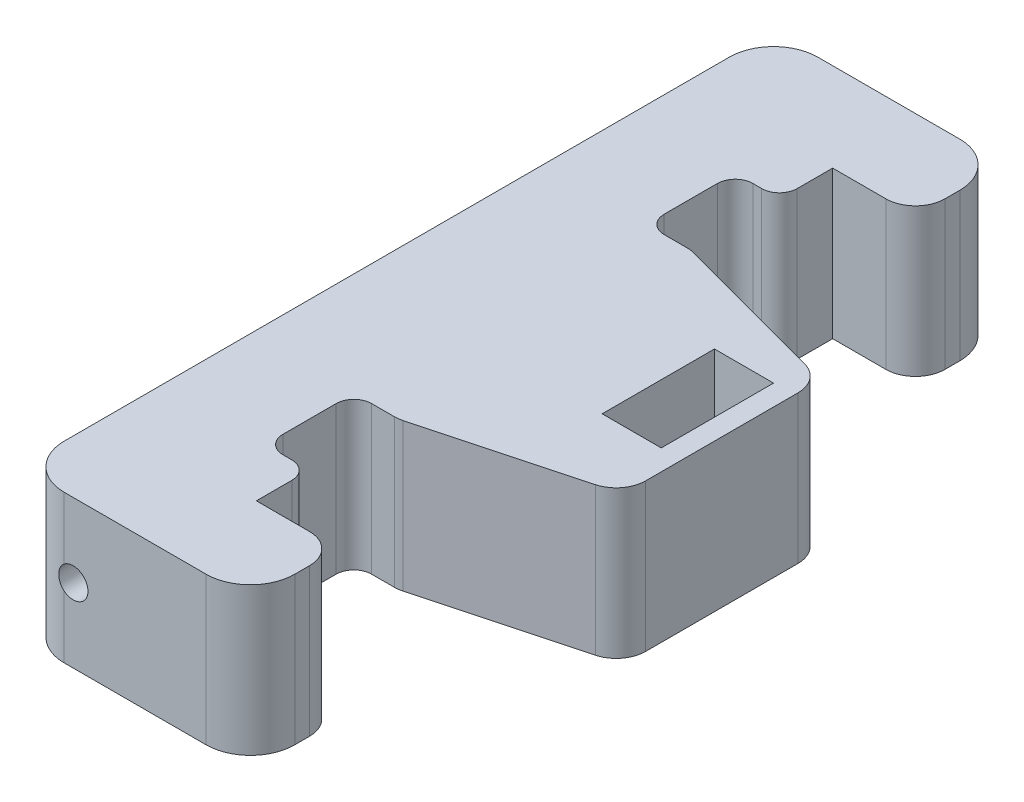
SolidWorks part; units mm, degrees
ref_plane "Front Plane" through (0, 0, 0) normal (0, 0, 1) x (1, 0, 0)
ref_plane "Top Plane" through (0, 0, 0) normal (0, 1, 0) x (1, 0, 0)
ref_plane "Right Plane" through (0, 0, 0) normal (1, 0, 0) x (0, 0, -1)
sketch "Sketch1" plane through (0, 0, 0) normal (0, 1, 0) x (1, 0, 0)
  line L0 (-13.97, 32.385) -> (13.97, -32.385) construction
  line L1 (-13.97, 32.385) -> (13.97, 32.385)
  line L2 (-13.97, 32.385) -> (-13.97, -32.385)
  line L3 (-13.97, -32.385) -> (13.97, -32.385)
  line L4 (13.97, 32.385) -> (13.97, -32.385)
  line L5 (-13.97, -32.385) -> (13.97, 32.385) construction
  line L7 (13.97, 32.385) -> (5.842, 32.385)
  line L8 (13.97, 32.385) -> (13.97, 12.573)
  line L9 (13.97, 12.573) -> (5.842, 12.573)
  line L10 (5.842, 32.385) -> (5.842, 12.573)
  line L11 (13.97, -32.385) -> (5.842, -32.385)
  line L12 (13.97, -32.385) -> (13.97, -12.573)
  line L13 (13.97, -12.573) -> (5.842, -12.573)
  line L14 (5.842, -32.385) -> (5.842, -12.573)
  line L15 (5.842, 12.573) -> (-1.27, 12.573)
  line L16 (5.842, 12.573) -> (5.842, 24.765)
  line L17 (5.842, 24.765) -> (-1.27, 24.765)
  line L18 (-1.27, 12.573) -> (-1.27, 24.765)
  line L23 (5.842, -12.573) -> (-1.27, -12.573)
  line L24 (5.842, -12.573) -> (5.842, -24.765)
  line L25 (5.842, -24.765) -> (-1.27, -24.765)
  line L26 (-1.27, -12.573) -> (-1.27, -24.765)
  line L28 (-1.27, 12.573) -> (-5.08, 12.573)
  line L29 (-1.27, 12.573) -> (-1.27, 20.193)
  line L30 (-1.27, 20.193) -> (-5.08, 20.193)
  line L31 (-5.08, 12.573) -> (-5.08, 20.193)
  line L32 (-1.27, -12.573) -> (-5.08, -12.573)
  line L33 (-1.27, -12.573) -> (-1.27, -20.193)
  line L34 (-1.27, -20.193) -> (-5.08, -20.193)
  line L35 (-5.08, -12.573) -> (-5.08, -20.193)
  point P4 (0, 0)
  dimension "D1" = 27.94
  dimension "D2" = 64.77
  dimension "D3" = 19.812
  dimension "D4" = 8.128
  dimension "D5" = 19.812
  dimension "D6" = 8.128
  dimension "D7" = 12.7
  dimension "D8" = 7.62
  dimension "D9" = 7.62
  dimension "D10" = 12.7
  dimension "D11" = 7.62
  dimension "D12" = 3.81
  dimension "D13" = 7.62
  dimension "D14" = 3.81
extrude "Boss-Extrude1" add sketch "Sketch1" along normal blind 12.7 contours L35 L32 L23 L15 L28 L31 L30 L18 L17 L10 L1 L2 L3 L14 L25 L26 L34 region at (-2.7087, 0, 0)
sketch "Sketch2" plane through (0, 12.7, 0) normal (0, 1, 0) x (1, 0, 0)
  line L19 (-1.27, 12.573) -> (13.97, 8.4895)
  line L20 (13.97, 12.573) -> (-5.08, 12.573) construction
  line L21 (13.97, 12.573) -> (13.97, -12.573) construction
  line L22 (-1.27, -12.573) -> (13.97, -8.4895)
  line L23 (13.97, -12.573) -> (-5.08, -12.573) construction
  line L24 (13.97, 8.4895) -> (13.97, 12.573)
  line L25 (13.97, 12.573) -> (-1.27, 12.573)
  line L26 (13.97, -8.4895) -> (13.97, -12.573)
  line L27 (13.97, -12.573) -> (-1.27, -12.573)
  dimension "D3" = 15
  dimension "D4" = 15
extrude "Cut-Extrude1" cut sketch "Sketch2" against normal through all
fillet "Fillet4" radius 1.524 6 edges at (-1.27, 6.35, 20.193) (-5.08, 6.35, 20.193) (-5.08, 6.35, 12.573) (-5.08, 6.35, -12.573) (-5.08, 6.35, -20.193) (-1.27, 6.35, -20.193)
fillet "Fillet5" radius 3.81 4 edges at (-13.97, 6.35, 32.385) (-13.97, 6.35, -32.385) (5.842, 6.35, -32.385) (5.842, 6.35, 32.385)
sketch "Sketch3" plane through (0, 0, 32.385) normal (0, 0, 1) x (1, 0, 0)
  line L0 (-10.16, 0) -> (2.032, 0) construction
  circle A0 centre (-9.392, 6.35) radius 1.27
  dimension "D1" = 2.54
  dimension "D2" = 6.35
extrude "Cut-Extrude2" cut sketch "Sketch3" against normal through all
sketch "Sketch4" plane through (0, 12.7, 0) normal (0, 1, 0) x (1, 0, 0)
  line L0 (0, 0) -> (13.97, 0) construction
  line L1 (7.112, 6.223) -> (12.192, 6.223)
  line L2 (7.112, 6.223) -> (7.112, -3.429)
  line L3 (7.112, -3.429) -> (12.192, -3.429)
  line L4 (12.192, 6.223) -> (12.192, -3.429)
  line L7 (13.97, 8.4895) -> (13.97, -8.4895) construction
  line L8 (-13.97, 28.575) -> (-13.97, -28.575) construction
  dimension "D1" = 9.652
  dimension "D2" = 6.223
  dimension "D3" = 21.082
  dimension "D4" = 5.08
extrude "Cut-Extrude3" cut sketch "Sketch4" against normal through all
fillet "Fillet6" radius 2.54 4 edges at (-1.27, 6.35, 12.573) (-1.27, 6.35, -12.573) (13.97, 6.35, 8.4895) (13.97, 6.35, -8.4895)
fillet "Fillet7" radius 2.54 2 edges at (5.842, 6.35, -24.765) (5.842, 6.35, 24.765)
